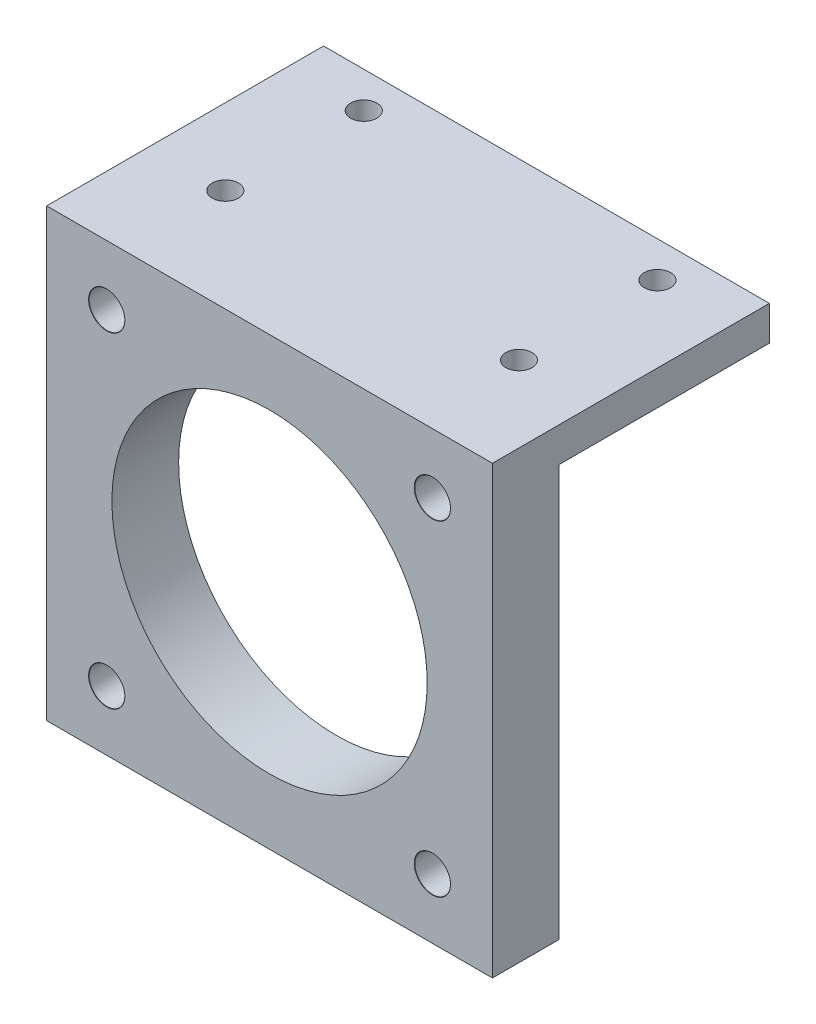
SolidWorks part; units mm, degrees
ref_plane "Front Plane" through (0, 0, 0) normal (0, 0, 1) x (1, 0, 0)
ref_plane "Top Plane" through (0, 0, 0) normal (0, 1, 0) x (1, 0, 0)
ref_plane "Right Plane" through (0, 0, 0) normal (1, 0, 0) x (0, 0, -1)
sketch "Sketch1" plane through (0, 0, 0) normal (0, 1, 0) x (1, 0, 0)
  line L0 (-21.209, 10) -> (-13.9706, 6.5871)
  line L1 (-21.209, -10) -> (21.209, -10)
  line L2 (-21.209, -10) -> (-21.209, 10)
  line L3 (-21.209, 10) -> (21.209, 10)
  line L4 (21.209, -10) -> (21.209, 10)
  line L5 (-21.209, -10) -> (21.209, 10) construction
  line L6 (-21.209, 10) -> (21.209, -10) construction
  line L7 (21.209, 10) -> (13.9706, 6.5871)
  line L8 (-21.209, -10) -> (-13.9706, -6.5871)
  line L9 (21.209, -10) -> (13.9706, -6.5871)
  point P0 (0, 0)
extrude "Boss-Extrude1" add sketch "Sketch1" along normal blind 6.35 contours L1 L4 L3 L2 region at (0, 0, 0)
hole_wizard "Tap Drill for M3x0.5 Tap2" positions "Sketch4" profile "Sketch5" hole size "M3x0.5" standard "ANSI Metric"
sketch "Sketch4" plane through (0, 0, 0) normal (0, -1, 0) x (-1, 0, 0)
  point P0 (-13.9706, 6.5871)
  point P3 (-13.9706, -6.5871)
  point P6 (13.9706, 6.5871)
  point P9 (13.9706, -6.5871)
sketch "Sketch5" plane through (13.9706, 0, -6.5871) normal (1, 0, 0) x (0, 0, -1)
  line L0 (0, 0) -> (0, 10)
  line L1 (0, 10) -> (1.25, 9.2489)
  line L2 (1.25, 9.2489) -> (1.25, 0.025)
  line L3 (1.25, 0.025) -> (1.275, 0)
  line L5 (1.275, 0) -> (0, 0)
  line L6 (-1.25, 0.025) -> (-1.275, 0) construction
  line L10 (0, 10) -> (-1.25, 9.2489) construction
  line L11 (0, -6.35) -> (0, 107.95) construction
  dimension "Hole Dia." = 2.5
  dimension "Hole Depth" = 10
  dimension "Near C'Sink Dia." = 2.55
  dimension "Near C'Sink Angle" = 90
  dimension "Drill Angle" = 118
sketch "Sketch12" plane through (0, 0, 10) normal (0, 0, 1) x (1, 0, 0)
  line L1 (-21.209, 6.35) -> (21.209, 6.35)
  line L2 (-21.209, 6.35) -> (-21.209, 0)
  line L3 (-21.209, 0) -> (21.209, 0)
  line L4 (21.209, 6.35) -> (21.209, 0)
extrude "Boss-Extrude2" add sketch "Sketch12" along normal blind 6.35
sketch "Sketch13" plane through (0, 0, 0) normal (0, -1, 0) x (1, 0, 0)
  line L0 (21.209, 16.35) -> (21.209, -10) construction
  line L1 (-21.209, 16.35) -> (21.209, 16.35)
  line L2 (-21.209, 16.35) -> (-21.209, 10)
  line L3 (-21.209, 10) -> (21.209, 10)
  line L4 (21.209, 16.35) -> (21.209, 10)
extrude "Boss-Extrude3" add sketch "Sketch13" along normal blind 36.068
sketch "Sketch14" plane through (0, 0, 16.35) normal (0, 0, 1) x (1, 0, 0)
  line L0 (21.209, 6.35) -> (15.494, 6.35)
  line L1 (21.209, 6.35) -> (-21.209, 6.35) construction
  line L2 (-21.209, 6.35) -> (-15.494, 6.35)
  line L3 (-15.494, 6.35) -> (-15.494, 0.635)
  line L4 (15.494, 6.35) -> (15.494, 0.635)
  line L5 (-21.209, -36.068) -> (-15.494, -36.068)
  line L6 (21.209, -36.068) -> (-21.209, -36.068) construction
  line L7 (-15.494, -36.068) -> (-15.494, -30.353)
  line L8 (21.209, -36.068) -> (15.494, -36.068)
  line L9 (15.494, -36.068) -> (15.494, -30.353)
hole_wizard "M3 Clearance Hole1" positions "Sketch15" profile "Sketch16" hole size "M3" standard "ANSI Metric" end condition through all
sketch "Sketch15" plane through (0, 0, 16.35) normal (0, 0, 1) x (1, 0, 0)
  point P0 (-15.494, 0.635)
  point P3 (15.494, 0.635)
  point P6 (15.494, -30.353)
  point P9 (-15.494, -30.353)
sketch "Sketch16" plane through (-15.494, 0.635, 16.35) normal (1, 0, 0) x (0, -1, 0)
  line L0 (0, 0) -> (0, 26.35)
  line L1 (0, 26.35) -> (1.7, 26.35)
  line L2 (1.7, 26.35) -> (1.7, 0.025)
  line L3 (1.7, 0.025) -> (1.725, 0)
  line L5 (1.725, 0) -> (0, 0)
  line L6 (-1.7, 0.025) -> (-1.725, 0) construction
  line L11 (0, -6.35) -> (0, 107.95) construction
  dimension "Thru Hole Dia." = 3.4
  dimension "Thru Hole Depth" = 26.35
  dimension "Near C'Sink Dia." = 3.45
  dimension "Near C'Sink Angle" = 90
sketch "Sketch17" plane through (0, 0, 0) normal (0, -1, 0) x (1, 0, 0)
  line L1 (-21.209, 10) -> (21.209, 10)
  line L2 (-21.209, 10) -> (-21.209, -10)
  line L3 (-21.209, -10) -> (21.209, -10)
  line L4 (21.209, 10) -> (21.209, -10)
extrude "Cut-Extrude1" cut sketch "Sketch17" against normal blind 3.068
sketch "Sketch19" plane through (0, 0, 16.35) normal (0, 0, 1) x (1, 0, 0)
  circle A0 centre (0, -14.859) radius 15
extrude "Cut-Extrude2" cut sketch "Sketch19" against normal through all
